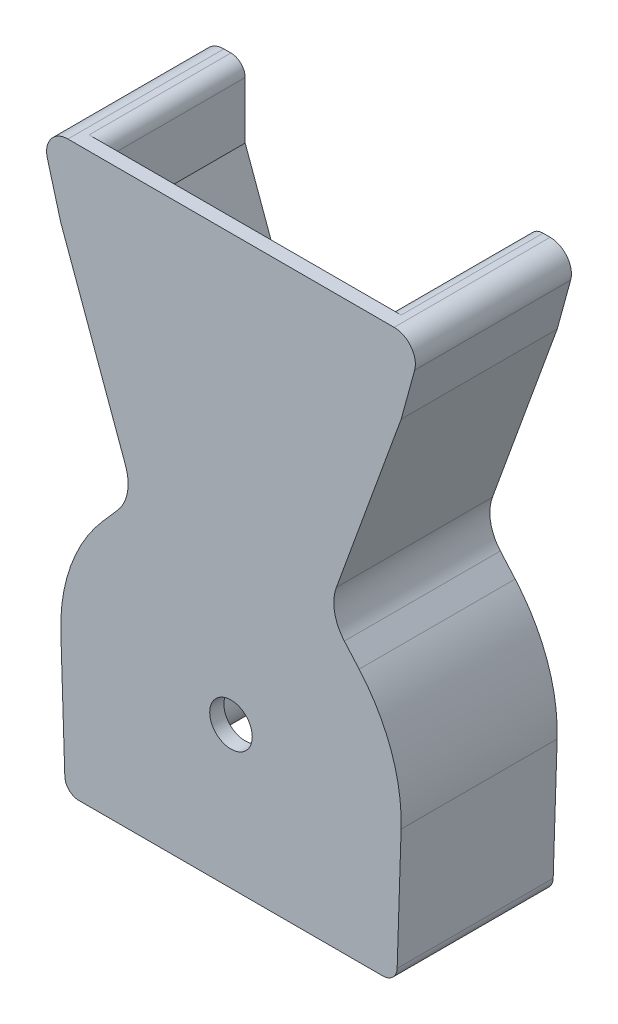
SolidWorks part; units mm, degrees
note: '?' marks a value the reader was unsure of.
ref_plane "Front Plane" through (0, 0, 0) normal (0, 0, 1) x (1, 0, 0)
ref_plane "Top Plane" through (0, 0, 0) normal (0, 1, 0) x (1, 0, 0)
ref_plane "Right Plane" through (0, 0, 0) normal (1, 0, 0) x (0, 0, -1)
sketch "Boundaries" plane through (0, 0, 0) normal (0, 0, 1) x (1, 0, 0)
  line L1 (-80, 100) -> (80, 100) construction
  line L2 (-80, 100) -> (-80, -100) construction
  line L3 (-80, -100) -> (80, -100) construction
  line L4 (80, 100) -> (80, -100) construction
  point P0 (0, 0)
  point P7 (0, 100)
  point P8 (80, 0)
  dimension "D1" = 160
  dimension "D2" = 200
sketch "Sketch2" plane through (0, 0, 0) normal (0, 0, 1) x (1, 0, 0)
  line L0 (-80, -100) -> (80, -100) construction
  line L1 (-53.1957, 0) -> (53.1957, 0) construction
  line L4 (-50, 75) -> (50, 75) construction
  line L5 (-50, 75) -> (-22.7022, 0)
  line L6 (50, 75) -> (22.7022, 0)
  line L7 (-53.1957, 0) -> (-22.7022, 0) construction
  line L8 (-80, 100) -> (-50, 100)
  line L9 (-80, 100) -> (-80, -100)
  line L10 (-80, -100) -> (-50, -100)
  line L11 (80, 100) -> (80, -100)
  line L12 (22.7022, 0) -> (53.1957, 0) construction
  line L13 (-50, 75) -> (-50, 100)
  line L14 (50, 75) -> (50, 100)
  line L15 (50, 100) -> (80, 100)
  line L16 (-37.6439, -17.092) -> (-22.7022, 0)
  line L17 (22.7022, 0) -> (37.6439, -17.092)
  line L18 (-50, -100) -> (-35.3553, -85.3553)
  line L19 (35.3553, -85.3553) -> (50, -100)
  line L20 (50, -100) -> (80, -100)
  line L21 (-50, -100) -> (50, -100) construction
  line L22 (-35.3553, -14.6447) -> (35.3553, -85.3553) construction
  line L23 (-35.3553, -85.3553) -> (35.3553, -14.6447) construction
  line L24 (0, 0) -> (0, -50) construction
  arc A0 (-37.6439, -17.092) -> (-35.3553, -85.3553) centre (0, -50) ccw construction
  arc A1 (-37.6439, -17.092) -> (-35.3553, -85.3553) centre (0, -50) ccw
  arc A2 (35.3553, -85.3553) -> (37.6439, -17.092) centre (0, -50) ccw construction
  arc A3 (35.3553, -85.3553) -> (37.6439, -17.092) centre (0, -50) ccw
  circle A4 centre (0, -50) radius 50 construction
  point P12 (0, 0)
  point P13 (0, 75)
  point P26 (0, -100)
  point P31 (0, -50)
  point P34 (0, -50)
  dimension "D1" = 100
  dimension "D2" = 45
  dimension "D3" = 45
  dimension "D4" = 70
  dimension "D5" = 70
  dimension "D8" = 100
  dimension "D9" = 75
  dimension "D10" = 45.4045
extrude "Boss-Extrude1" add sketch "Sketch2" against normal blind 50
sketch "Sketch3" plane through (0, 0, 0) normal (0, 0, 1) x (1, 0, 0)
  line L0 (-29.9816, 20) -> (29.9816, 20)
  line L1 (-50, 75) -> (-22.7022, 0) construction
  line L2 (50, 75) -> (22.7022, 0) construction
  line L3 (29.9816, 20) -> (22.7022, 0)
  line L4 (22.7022, 0) -> (-22.7022, 0)
  line L5 (-22.7022, 0) -> (-29.9816, 20)
  dimension "D1" = 20
extrude "Boss-Extrude2" add sketch "Sketch3" against normal blind 10
chamfer "Chamfer1" distance 20 distance2 15 1 edges at (0, 20, -10) first distance on face at (0, 10, -10)
sketch "Sketch4" plane through (0, 0, 0) normal (0, 0, 1) x (1, 0, 0)
  line L1 (-80, 100) -> (80, 100)
  line L2 (-80, 100) -> (-80, -100)
  line L3 (-80, -100) -> (80, -100)
  line L4 (80, 100) -> (80, -100)
extrude "Boss-Extrude3" add sketch "Sketch4" along normal blind 5
fillet "Fillet1" radius 10 5 edges at (-35.3553, -85.3553, -25) (35.3553, -85.3553, -25) (-22.7022, 0, -30) (22.7022, 0, -30) (0, 13.3333, 0)
sketch "Sketch5" plane through (0, 0, 0) normal (0, 0, -1) x (-1, 0, 0)
  circle A0 centre (0, -50) radius 7.5
  dimension "D1" = 15
extrude "Cut-Extrude1" cut sketch "Sketch5" against normal up to surface (5 mm away) up to face at (0, 0, 5)
sketch "Sketch8" plane through (0, 0, -50) normal (0, 0, -1) x (-1, 0, 0)
  line L0 (-60, 100) -> (-80, 100)
  line L1 (-50, 100) -> (-50, 75) construction
  line L2 (-50, 75) -> (-24.7233, 5.5529) construction
  line L3 (-26.5915, -4.4489) -> (-37.6439, -17.092) construction
  line L6 (-26.5915, -4.4489) -> (-37.6439, -17.092) construction
  line L7 (-50, 75) -> (-24.7233, 5.5529) construction
  line L8 (-50, 100) -> (-50, 75) construction
  line L10 (-60, 73.2367) -> (-34.1202, 2.1327)
  line L11 (-34.1202, 2.1327) -> (-45.1727, -10.5104)
  line L13 (-80, 100) -> (-80, -100)
  line L15 (-48.9041, -84.7619) -> (-50.9313, -86.7892) construction
  line L16 (0, -100) -> (0, 100) construction
  line L17 (50, -100) -> (-50, -100) construction
  line L18 (-50, 100) -> (50, 100) construction
  line L27 (-58.8989, -85.0845) -> (-59.9688, -51.9355)
  line L28 (-64.7336, 90.5187) -> (-60, 73.2367)
  line L29 (-41.833, -91.833) -> (-43.8603, -93.8603) construction
  line L31 (-80, 100) -> (-50, 100) construction
  line L32 (-60, 100) -> (-60, 73.2367) construction
  line L33 (-60, 100) -> (-57.5, 100)
  line L44 (-58.8989, -85.0845) -> (-58.4175, -100)
  line L45 (-80, -100) -> (-58.4175, -100)
  line L46 (-50, -100) -> (-80, -100) construction
  line L47 (34.1202, 2.1327) -> (45.1727, -10.5104)
  line L48 (58.8989, -85.0845) -> (59.9688, -51.9355)
  line L49 (58.8989, -85.0845) -> (58.4175, -100)
  line L50 (80, -100) -> (58.4175, -100)
  line L51 (80, 100) -> (80, -100)
  line L52 (60, 100) -> (57.5, 100)
  line L53 (60, 100) -> (80, 100)
  line L54 (64.7336, 90.5187) -> (60, 73.2367)
  line L55 (60, 73.2367) -> (34.1202, 2.1327)
  arc A0 (-26.5915, -4.4489) -> (-24.7233, 5.5529) centre (-34.1202, 2.1327) ccw construction
  arc A1 (-37.6439, -17.092) -> (-40.7534, -78.9683) centre (0, -50) ccw construction
  arc A2 (-41.833, -91.833) -> (-40.7534, -78.9683) centre (-48.9041, -84.7619) ccw construction
  arc A3 (-41.833, -91.833) -> (-40.7534, -78.9683) centre (-48.9041, -84.7619) ccw construction
  arc A4 (-37.6439, -17.092) -> (-40.7534, -78.9683) centre (0, -50) ccw construction
  arc A5 (-26.5915, -4.4489) -> (-24.7233, 5.5529) centre (-34.1202, 2.1327) ccw construction
  arc A6 (-34.1202, 2.1327) -> (-34.1202, 2.1327) centre (-34.1202, 2.1327) ccw
  arc A7 (-45.1727, -10.5104) -> (-59.9688, -51.9355) centre (0, -50) ccw
  arc A8 (-48.9041, -84.7619) -> (-48.9041, -84.7619) centre (-48.9041, -84.7619) ccw
  arc A9 (-45.1727, -10.5104) -> (-48.9041, -84.7619) centre (0, -50) ccw construction
  circle A12 centre (-48.9041, -84.7619) radius 2 construction
  arc A13 (-41.833, -91.833) -> (-58.8989, -85.0845) centre (-48.9041, -84.7619) cw construction
  circle A15 centre (-57.5, 92.5) radius 7.5 construction
  arc A16 (-64.7336, 90.5187) -> (-57.5, 100) centre (-57.5, 92.5) cw
  circle A17 centre (-57.5, 92.5) radius 2 construction
  arc A21 (45.1727, -10.5104) -> (59.9688, -51.9355) centre (0, -50) cw
  arc A22 (64.7336, 90.5187) -> (57.5, 100) centre (57.5, 92.5) ccw
  point P33 (0, 0)
  dimension "D3" = 4
  dimension "D2" = 15
  dimension "D4" = 10
  dimension "D1" = 10
extrude "Cut-Extrude3" cut sketch "Sketch8" against normal up to surface (55 mm away)
fillet "Fillet3" radius 15 2 edges at (34.1202, 2.1327, -22.5) (-34.1202, 2.1327, -22.5)
fillet "Fillet4" radius 5 2 edges at (-50, 100, -25) (50, 100, -25)
sketch "Sketch9" plane through (0, 0, -50) normal (0, 0, -1) x (-1, 0, 0)
  line L0 (0, -100) -> (0, 100) construction
  line L1 (50, -100) -> (-50, -100) construction
  line L2 (-55, 100) -> (55, 100) construction
  line L3 (-50, 95) -> (-50, 75) construction
  line L4 (-57.5, 100) -> (-55, 100) construction
  line L5 (-48.9391, -85.5982) -> (-38.9391, -85.5982) construction
  circle A0 centre (-57.5, 92.5) radius 2
  circle A1 centre (-48.9391, -85.5982) radius 2
  arc A4 (-41.833, -91.833) -> (-40.7534, -78.9683) centre (-48.9041, -84.7619) ccw construction
  circle A5 centre (48.9391, -85.5982) radius 2
  circle A6 centre (57.5, 92.5) radius 2
  dimension "D3" = 4
  dimension "D1" = 7.5
  dimension "D2" = 7.5
  dimension "D5" = 10
extrude "Cut-Extrude4" cut sketch "Sketch9" against normal blind 10
fillet "Fillet6" radius 5 2 edges at (-58.4175, -100, -22.5) (58.4175, -100, -22.5)
ref_plane "MidPlane" through (0, 0, -25) normal (0, 0, -1) x (-1, 0, 0)
ref_axis "Food Drop Axis" through (0, 124.9402, -25) along (0, -1, 0)?
